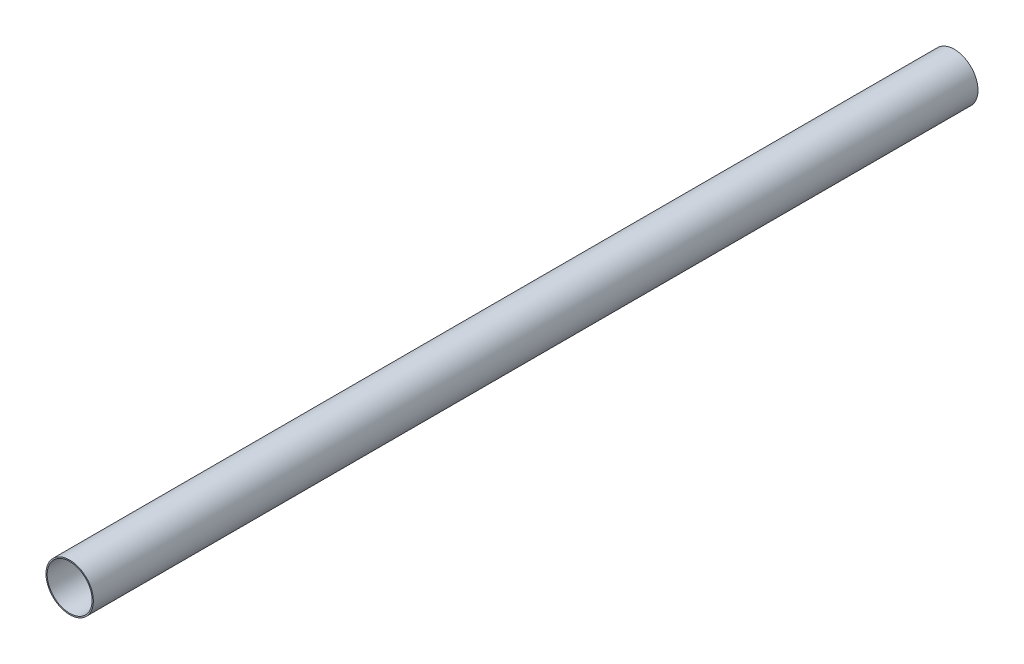
SolidWorks part; units mm, degrees
ref_plane "Ebene vorne" through (0, 0, 0) normal (0, 0, 1) x (1, 0, 0)
ref_plane "Ebene oben" through (0, 0, 0) normal (0, 1, 0) x (1, 0, 0)
ref_plane "Ebene rechts" through (0, 0, 0) normal (1, 0, 0) x (0, 0, -1)
sketch "Skizze1" plane through (0, 0, 0) normal (0, 0, 1) x (1, 0, 0)
  circle A3 centre (0, 0) radius 37.5
  dimension "D1" = 75
extrude "Aufsatz-Linear austragen2" add sketch "Skizze1" along normal blind 1400 contours A3
shell "Wandung2" thickness 1.9 removed face at (37.5, 0, 0) removed face at (37.5, 0, 1400)
ref_axis "Achse1" through (0, 0, 2170.4866) along (0, 0, -1)
